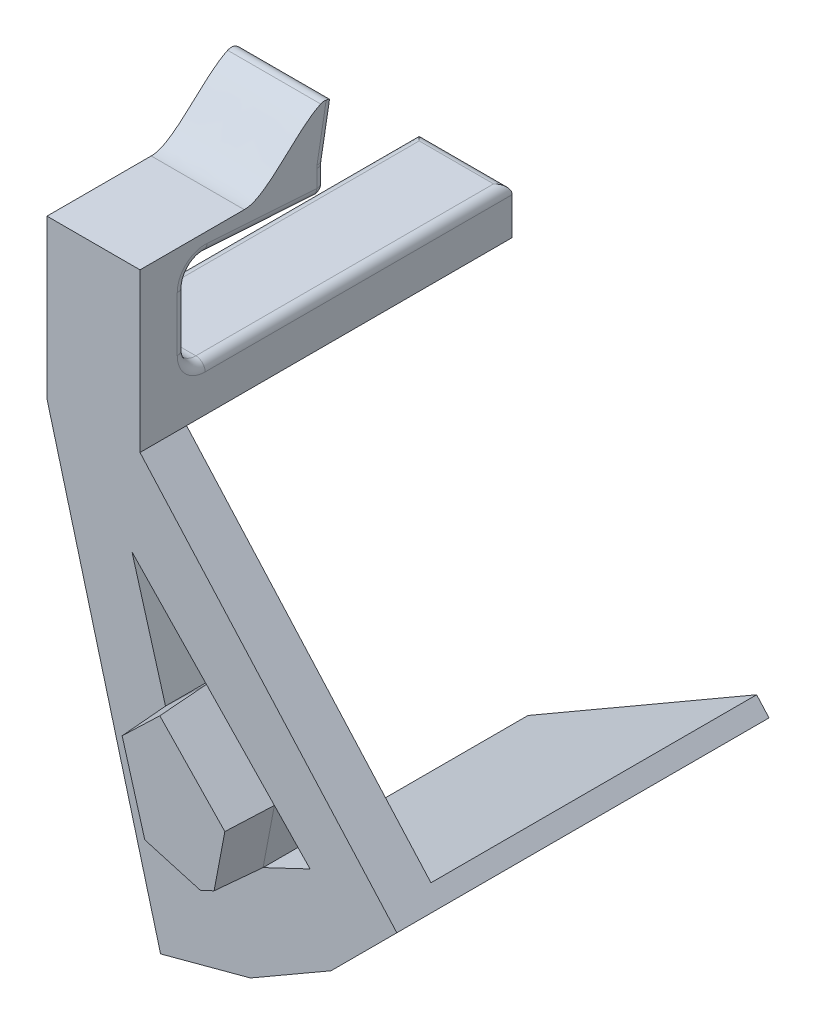
SolidWorks part; units mm, degrees
ref_plane "Front Plane" through (0, 0, 0) normal (0, 0, 1) x (1, 0, 0)
ref_plane "Top Plane" through (0, 0, 0) normal (0, 1, 0) x (1, 0, 0)
ref_plane "Right Plane" through (0, 0, 0) normal (1, 0, 0) x (0, 0, -1)
sketch "Sketch2" plane through (0, 0, 0) normal (1, 0, 0) x (0, 0, -1)
  line L0 (20, 17) -> (21.058, 23)
  line L1 (0, 0) -> (5, 0)
  line L2 (0, 0) -> (0, 17)
  line L3 (0, 17) -> (5, 17)
  line L4 (5, 0) -> (5, 17)
  line L6 (5, 0) -> (5, 7)
  line L9 (5, 17) -> (20, 17)
  line L10 (5, 17) -> (5, 15)
  line L11 (5, 15) -> (20, 15) construction
  line L12 (20, 17) -> (20, 15)
  line L13 (5, 5) -> (40, 5)
  line L14 (5, 5) -> (5, 0)
  line L15 (5, 0) -> (40, 0)
  line L16 (40, 5) -> (40, 0)
  line L20 (11.2016, 17) -> (20, 17)
  line L23 (20, 15) -> (20, 15.0689)
  line L24 (18.9335, 14.0711) -> (5, 15)
  arc A1 (20, 15.0689) -> (18.9335, 14.0711) centre (19, 15.0689) cw
  spline S0 degree 3 poles (11.2016, 17) (14.1868, 16.9552) (17.9632, 23.5457) (21.058, 23) knots 0 0 0 0 1 1 1 1
  point P25 (20, 14)
  dimension "D3" = 6
  dimension "D12" = 1
  dimension "D2" = 80
  dimension "D6" = 10
  dimension "D7" = 2
  dimension "D8" = 5
  dimension "D9" = 15
  dimension "D10" = 35
  dimension "D11" = 1
extrude "Boss-Extrude1" add sketch "Sketch2" along normal blind 10 contours L1 L4 L3 L2 | L4 | L16 L13 L4 L15 | L12 L9 L4 L11 | L9 L0 | L11 L24 A1 L23 region at (0, 19.3214, -17.7298) region at (0, 15.7432, -12.9546) region at (0, 8.5, -2.5) region at (0, 2.5, -22.5)
sketch "Sketch4" plane through (0, 0, 0) normal (0, 0, 1) x (1, 0, 0)
  line L0 (10, 0) -> (-2.2086, -45.5631)
  line L1 (-2.2086, -45.5631) -> (-11.8678, -42.9749)
  line L2 (-11.8678, -42.9749) -> (-20.5281, -37.9749)
  line L3 (-20.5281, -37.9749) -> (-27.5992, -30.9038)
  line L4 (-27.5992, -30.9038) -> (0, 0)
  line L6 (0, 0) -> (10, 0)
  line L7 (10, 0) -> (0, 0) construction
  line L8 (10, 5) -> (-3.4586, -45.2281) construction
  line L9 (10, 5) -> (0, 5) construction
  line L10 (10, 0) -> (10, 17) construction
  line L11 (-18.2774, -29.6218) -> (-6.4709, -35.2264)
  line L12 (-6.4709, -35.2264) -> (0.8649, -9.6768)
  line L13 (0.8649, -9.6768) -> (-18.2774, -29.6218)
  dimension "D1" = 15
  dimension "D2" = 165
  dimension "D3" = 165
  dimension "D4" = 10
  dimension "D5" = 52
extrude "Boss-Extrude2" add sketch "Sketch4" against normal up to surface (5 mm away) up to face at (5, 10, -5)
sketch "Sketch5" plane through (0, 0, -5) normal (0, 0, -1) x (-1, 0, 0)
  line L0 (2.2086, -45.5631) -> (11.8678, -42.9749)
  line L1 (11.8678, -42.9749) -> (20.5281, -37.9749)
  line L2 (20.5281, -37.9749) -> (27.5992, -30.9038)
  line L3 (27.5992, -30.9038) -> (26.267, -29.4121)
  line L4 (27.5992, -30.9038) -> (0, 0) construction
  line L5 (26.267, -29.4121) -> (1.691, -43.6312)
  line L6 (-10, 0) -> (2.2086, -45.5631) construction
  line L7 (1.691, -43.6312) -> (2.2086, -45.5631)
  dimension "D1" = 2
extrude "Boss-Extrude3" add sketch "Sketch5" along normal blind 35
fillet "Fillet1" radius 2 2 edges at (5, 5, -5) (5, 15, -5)
fillet "Fillet2" radius 1 19 edges at (0, 14.3386, -19.6832) (10, 14.3386, -19.6832) (0, 14.3227, -5.6336) (0, 9.9311, -5) (0, 5.5858, -5.5858) (0, 14.4644, -13.0333) (0, 5, -23.5) (5, 5, -40) (10, 5, -23.5) (10, 5.5858, -5.5858) (10, 9.9311, -5) (10, 14.3227, -5.6336) (10, 14.4644, -13.0333) (0, 20, -20.529) (10, 20, -20.529) (5, 23, -21.058) (10, 16.0344, -20) (0, 16.0344, -20) (5, 17, -20)
ref_plane "Plane1" through (5, 0, 0) normal (1, 0, 0) x (0, 0, -1)
mirror "Mirror2" about plane through (5, 0, 0) normal (1, 0, 0) of "Boss-Extrude3", "Boss-Extrude2"
sketch "Sketch6" plane through (0, 0, -5) normal (0, 0, -1) x (-1, 0, 0)
  line L0 (0, 0) -> (-12.2086, -45.5631)
  line L1 (-5, -18.6603) -> (-11.691, -43.6312) construction
  line L2 (-12.2086, -45.5631) -> (1.179, -62.7339)
  line L3 (1.179, -62.7339) -> (43.8323, -23.3566)
  line L4 (43.8323, -23.3566) -> (0, 0)
  line M3 (-11.691, -43.6312) -> (-5, -18.6603)
  line M4 (-5, -18.6603) -> (1.691, -43.6312)
  line M5 (1.691, -43.6312) -> (26.267, -29.4121)
  line M6 (26.267, -29.4121) -> (0, 0)
  line M11 (18.2774, -29.6218) -> (6.4709, -35.2264)
  line M12 (6.4709, -35.2264) -> (-0.8649, -9.6768)
  line M13 (-0.8649, -9.6768) -> (18.2774, -29.6218)
extrude "Cut-Extrude1" cut sketch "Sketch6" against normal through all contours L3 L4 L0 L2 M6 M5 M4 M3 | L0 M6 M4 M5 M13 M11 M12 | M11 M13 M12 region at (-12.7331, -15.0636, -5) region at (-21.5205, -12.4207, -5) region at (-7.9611, -24.8416, -5)
delete or keep bodies "Body-Delete/Keep 1" type delete bodies bodies 108
sketch "Sketch7" plane through (0, 0, 0) normal (0, 0, 1) x (1, 0, 0)
  line L8 (9.1351, -9.6768) -> (28.2774, -29.6218) construction
  line L9 (24.441, -25.6245) -> (17.1367, -18.0139)
  line L10 (17.1367, -18.0139) -> (12.7404, -22.2334)
  line L11 (16.4709, -35.2264) -> (9.1351, -9.6768) construction
  line L12 (12.7404, -22.2334) -> (15.2662, -31.0305)
  line L16 (23.2246, -32.0204) -> (21.5237, -32.8278)
  line L17 (28.2774, -29.6218) -> (16.4709, -35.2264) construction
  line L18 (21.5237, -32.8278) -> (15.2662, -31.0305)
  line L19 (24.441, -25.6245) -> (23.2246, -32.0204)
  point P2 (22.3741, -32.4241)
extrude "Boss-Extrude6" add sketch "Sketch7" against normal up to surface (5 mm away) up to face at (17.9611, -24.8416, -5)
sketch "Sketch8" plane through (0, 0, 0) normal (0, 0, 1) x (1, 0, 0)
  line L12 (21.5237, -32.8278) -> (23.2246, -32.0204)
  line L13 (15.2662, -31.0305) -> (21.5237, -32.8278)
  line L14 (12.7404, -22.2334) -> (15.2662, -31.0305)
  line L15 (17.1367, -18.0139) -> (12.7404, -22.2334)
  line L16 (24.441, -25.6245) -> (17.1367, -18.0139)
  line L17 (23.2246, -32.0204) -> (24.441, -25.6245)
  line L18 (21.5237, -32.8278) -> (23.2246, -32.0204)
  line L19 (15.2662, -31.0305) -> (21.5237, -32.8278)
  line L20 (12.7404, -22.2334) -> (15.2662, -31.0305)
  line L21 (17.1367, -18.0139) -> (12.7404, -22.2334)
  line L22 (24.441, -25.6245) -> (17.1367, -18.0139)
  line L23 (23.2246, -32.0204) -> (24.441, -25.6245)
  dimension "D1" = 0
ref_plane "Plane2" through (0, 0, 5) normal (0, 0, 1) x (1, 0, 0)
sketch "Sketch9" plane through (0, 0, 5) normal (0, 0, 1) x (1, 0, 0)
  line L12 (21.4975, -32.5082) -> (22.9584, -31.8147)
  line L13 (22.9584, -31.8147) -> (24.1173, -25.7205)
  line L14 (24.1173, -25.7205) -> (17.128, -18.4381)
  line L15 (17.128, -18.4381) -> (13.0786, -22.3245)
  line L16 (13.0786, -22.3245) -> (15.5087, -30.788)
  line L17 (15.5087, -30.788) -> (21.4975, -32.5082)
  line L18 (21.4975, -32.5082) -> (22.9584, -31.8147)
  line L19 (22.9584, -31.8147) -> (24.1173, -25.7205)
  line L20 (24.1173, -25.7205) -> (17.128, -18.4381)
  line L21 (17.128, -18.4381) -> (13.0786, -22.3245)
  line L22 (13.0786, -22.3245) -> (15.5087, -30.788)
  line L23 (15.5087, -30.788) -> (21.4975, -32.5082)
  dimension "D1" = 0.3
loft "Loft1" add profiles "Sketch9", "Sketch8" connector at (13.0786, -22.3245, 5) connector at (12.7404, -22.2334, 0)
